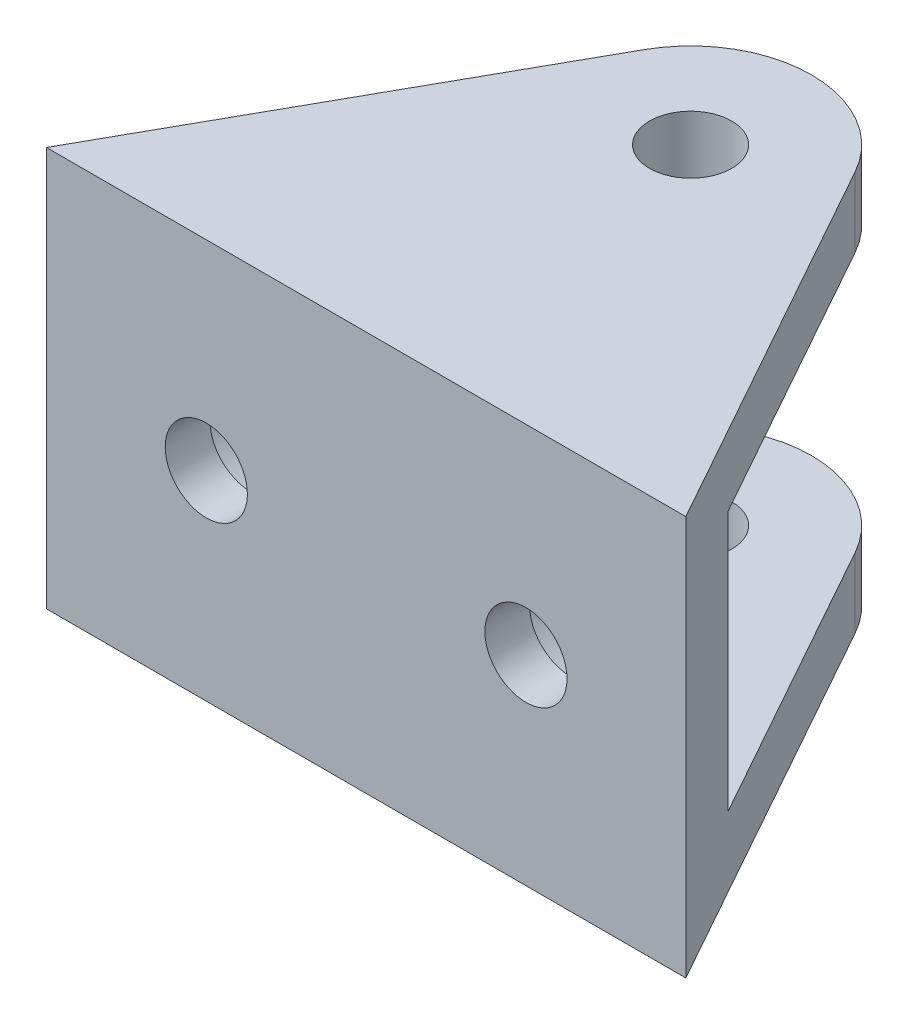
SolidWorks part; units mm, degrees
material "6061-T6 (SS)"
ref_plane "X-Y Datum" through (0, 0, 0) normal (0, 0, 1) x (1, 0, 0)
ref_plane "X-Z Datum" through (0, 0, 0) normal (0, 1, 0) x (1, 0, 0)
ref_plane "Y-Z Datum" through (0, 0, 0) normal (1, 0, 0) x (0, 0, -1)
sketch "Sketch1" plane through (0, 0, 0) normal (1, 0, 0) x (0, 0, -1)
  line L0 (0, 0) -> (0, 31.75)
  line L1 (0, 31.75) -> (38.4801, 31.75)
  line L2 (38.4801, 31.75) -> (38.4801, 26.2001)
  line L3 (38.4801, 26.2001) -> (7.62, 26.2001)
  line L4 (7.62, 26.2001) -> (7.62, 5.5499)
  line L5 (7.62, 5.5499) -> (38.4801, 5.5499)
  line L6 (38.4801, 5.5499) -> (38.4801, 0)
  line L7 (38.4801, 0) -> (0, 0)
  line L8 (25.7801, 31.75) -> (25.7801, 0) construction
  dimension "D1" = 20.6502
  dimension "D2" = 31.75
  dimension "D3" = 12.7
  dimension "D4" = 7.62
extrude "Boss-Extrude1" add sketch "Sketch1" along normal blind 50.8
sketch "Sketch2" plane through (0, 0, -7.62) normal (0, 0, -1) x (-1, 0, 0)
  line L0 (-50.8, 15.875) -> (0, 15.875) construction
  line L1 (-50.8, 5.5499) -> (-50.8, 26.2001) construction
  line L2 (0, 5.5499) -> (0, 26.2001) construction
  line L3 (-25.4, 5.5499) -> (-25.4, 26.2001) construction
  line L4 (-50.8, 5.5499) -> (0, 5.5499) construction
  line L5 (-50.8, 26.2001) -> (0, 26.2001) construction
  point P6 (-38.1, 15.875)
  point P7 (-12.7, 15.875)
  dimension "D1" = 25.4
  dimension "D2" = 12.7
hole_wizard "CBORE for 1/4 Binding Head Machine Screw1" positions "Sketch2" profile "Sketch3" counterbore size "1/4" standard "ANSI Inch" end condition through all
sketch "Sketch3" plane through (12.7, 15.875, -7.62) normal (1, 0, 0) x (0, 1, 0)
  line L0 (0, 0) -> (0, 7.62)
  line L1 (0, 7.62) -> (3.2639, 7.62)
  line L3 (3.2639, 7.62) -> (3.2639, 4.064)
  line L4 (3.2639, 4.064) -> (7.1437, 4.064)
  line L5 (7.1437, 4.064) -> (7.1437, 0)
  line L7 (7.1437, 0) -> (0, 0)
  line L11 (0, -6.35) -> (0, 107.95) construction
  dimension "Thru Hole Dia." = 6.5278
  dimension "Thru Hole Depth" = 7.62
  dimension "C'Bore Dia." = 14.2875
  dimension "C'Bore Depth" = 4.064
sketch "Sketch4" plane through (0, 0, 0) normal (0, -1, 0) x (1, 0, 0)
  line L0 (25.4, 0) -> (25.4, -38.4801) construction
  line L1 (50.8, 0) -> (0, 0) construction
  line L2 (50.8, -38.4801) -> (0, -38.4801) construction
  line L3 (17.0053, -30.4658) -> (0, 0)
  line L4 (33.7947, -30.4658) -> (50.8, 0)
  line L5 (0, 0) -> (0, -38.4801)
  line L6 (0, -38.4801) -> (50.8, -38.4801)
  line L7 (50.8, -38.4801) -> (50.8, 0)
  circle A0 centre (25.4, -25.7801) radius 3.2639
  arc A1 (17.0053, -30.4658) -> (33.7947, -30.4658) centre (25.4, -25.7801) ccw
  dimension "D1" = 6.5278
  dimension "D2" = 6.35
extrude "Cut-Extrude1" cut sketch "Sketch4" against normal up to surface (31.75 mm away) up to face at (25.4, 31.75, -19.2401)
